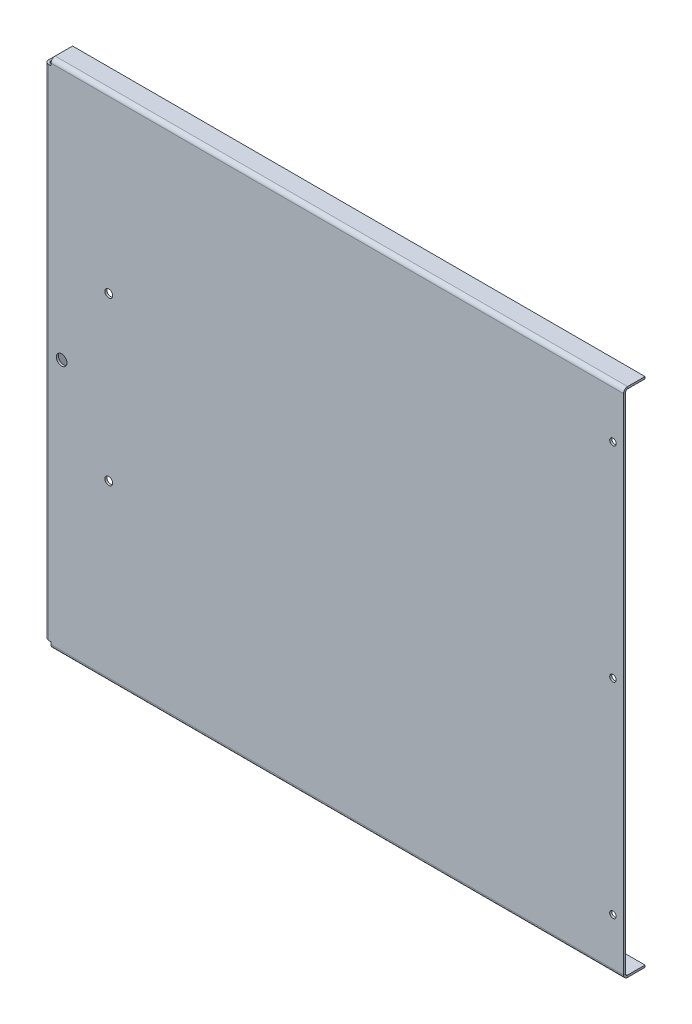
SolidWorks part; units mm, degrees
note: The reader was unsure of these and kept them because the rebuilt part matched: flange length of "Brida de arista1".
ref_plane "Alzado" through (0, 0, 0) normal (0, 0, 1) x (1, 0, 0)
ref_plane "Planta" through (0, 0, 0) normal (0, 1, 0) x (1, 0, 0)
ref_plane "Vista lateral" through (0, 0, 0) normal (1, 0, 0) x (0, 0, -1)
sketch "Croquis1" plane through (0, 0, 0) normal (0, 0, 1) x (1, 0, 0)
  line L1 (-215.519, -190.5) -> (215.519, -190.5)
  line L2 (-215.519, -190.5) -> (-215.519, 190.5)
  line L3 (-215.519, 190.5) -> (215.519, 190.5)
  line L4 (215.519, -190.5) -> (215.519, 190.5)
  line L5 (-215.519, -190.5) -> (215.519, 190.5) construction
  line L6 (-215.519, 190.5) -> (215.519, -190.5) construction
  point P0 (0, 0)
  dimension "D1" = 381
  dimension "D2" = 431.038
base flange "Brida base1" sketch "Croquis1" thickness 1.524 reverse thickness direction no parameters "D1"=1.524
sketch "Croquis6" plane through (0, 0, 0) normal (0, 0, 1) x (1, 0, 0)
  line L1 (-215.519, 190.5) -> (-210.693, 190.5)
  line L2 (-215.519, 190.5) -> (-215.519, 185.674)
  line L3 (-215.519, 185.674) -> (-210.693, 185.674)
  line L4 (-210.693, 190.5) -> (-210.693, 185.674)
  line L5 (-215.519, -190.5) -> (-210.693, -190.5)
  line L6 (-215.519, -190.5) -> (-215.519, -185.674)
  line L7 (-215.519, -185.674) -> (-210.693, -185.674)
  line L8 (-210.693, -190.5) -> (-210.693, -185.674)
  dimension "D1" = 4.826
  dimension "D2" = 4.826
extrude "Cortar-Extruir1" cut sketch "Croquis6" against normal up to next normal cut yes
edge flange "Brida de arista1" sketch "Croquis13" flange profiles "Croquis13", "Croquis14", "Croquis15" flange angle 90 flange length 16.002 flange position material inside bend radius 1.524 thickness 1.524 relief rectangular gap distance 1 parameters "D6"=10, "D8"=1
sketch "Croquis13" plane through (0, 190.5, -1.524) normal (0, 1, 0) x (1, 0, 0)
  line L0 (215.519, 0) -> (-210.693, 0) construction
  line L1 (215.519, 0) -> (-210.693, 0)
  line L2 (-210.693, 0) -> (-210.693, 14.478)
  line L3 (-210.693, 14.478) -> (215.519, 14.478)
  line L4 (215.519, 14.478) -> (215.519, 0)
sketch "Croquis14" plane through (0, -190.5, -1.524) normal (0, -1, 0) x (-1, 0, 0)
  line L0 (210.693, 0) -> (-215.519, 0) construction
  line L1 (210.693, 0) -> (-215.519, 0)
  line L2 (-215.519, 0) -> (-215.519, 14.478)
  line L3 (-215.519, 14.478) -> (210.693, 14.478)
  line L4 (210.693, 14.478) -> (210.693, 0)
sketch "Croquis15" plane through (-215.519, 0, -1.524) normal (-1, 0, 0) x (0, 1, 0)
  line L0 (185.674, 0) -> (-185.674, 0) construction
  line L1 (185.674, 0) -> (-185.674, 0)
  line L2 (-185.674, 0) -> (-185.674, 14.478)
  line L3 (-185.674, 14.478) -> (185.674, 14.478)
  line L4 (185.674, 14.478) -> (185.674, 0)
bend "Pliegue de arista1" bend radius 1.524 bend angle 90 parameters "D5"=1
bend "Pliegue de arista2" bend radius 1.524 bend angle 90 parameters "D5"=2
bend "Pliegue de arista3" bend radius 1.524 bend angle 90 parameters "D5"=3
sketch "Croquis16" plane through (0, 0, 0) normal (0, 0, 1) x (1, 0, 0)
  line L0 (215.519, -187.452) -> (215.519, 187.452) construction
  line L1 (215.519, 190.5) -> (-210.693, 190.5) construction
  line L2 (-210.693, -190.5) -> (215.519, -190.5) construction
  circle A0 centre (-202.819, 0) radius 3.9624
  circle A1 centre (-167.767, 60.452) radius 2.8956
  circle A2 centre (-167.767, -60.452) radius 2.8956
  circle A3 centre (207.645, 152.4) radius 2.413
  circle A4 centre (207.645, 0) radius 2.413
  circle A5 centre (207.645, -152.4) radius 2.413
  dimension "D1" = 60.452
  dimension "D2" = 60.452
  dimension "D8" = 4.826
  dimension "D9" = 5.7912
  dimension "D10" = 7.9248
  dimension "D3" = 383.286
  dimension "D4" = 418.338
  dimension "D5" = 38.1
  dimension "D6" = 38.1
  dimension "D7" = 7.874
extrude "Cortar-Extruir2" cut sketch "Croquis16" against normal up to next normal cut yes
sketch "Líneas de pliegue1" [suppressed] plane through (0, 0, 0) normal (0, 1, 0) x (1, 0, 0)
sketch "Cuadro delimitador1" [suppressed] plane through (0, 0, 0) normal (0, 1, 0) x (1, 0, 0)
sheet metal parameters "Chapa metálica1" thickness 1.524 parameters "D1"=1.524
flat pattern "Chapa desplegada1" [suppressed]
sketch "Líneas de pliegue2" plane through (0, 0, 0) normal (0, 1, 0) x (1, 0, 0)
sketch3d "Cuadro delimitador2" [suppressed]
  line L0 (215.519, -190.5, 0) -> (-215.519, -190.5, 0) construction
  line L1 (215.519, 190.5, 0) -> (-215.519, 190.5, 0) construction
  line L2 (215.519, -190.5, 0) -> (215.519, 190.5, 0) construction
  line L3 (-215.519, -190.5, 0) -> (-215.519, 190.5, 0) construction
sheet metal parameters "Chapa metálica2" thickness 1.524 parameters "D1"=1.524
flat pattern "Chapa desplegada1"
sketch "Líneas de pliegue2" plane through (0, 0, 0) normal (0, 1, 0) x (1, 0, 0)
sketch3d "Cuadro delimitador2" [suppressed]
  line L0 (-215.519, -190.5, 0) -> (215.519, -190.5, 0) construction
  line L1 (-215.519, 190.5, 0) -> (215.519, 190.5, 0) construction
  line L2 (-215.519, -190.5, 0) -> (-215.519, 190.5, 0) construction
  line L3 (215.519, -190.5, 0) -> (215.519, 190.5, 0) construction
sheet metal parameters "Chapa metálica3" thickness 1.524 parameters "D1"=1.524
flat pattern "Chapa desplegada1"
sketch "Líneas de pliegue2" plane through (0, 0, 0) normal (0, 0, 1) x (1, 0, 0)
  line L0 (-214.2425, 185.674) -> (-214.2425, -185.674) construction
  line L1 (-210.693, -189.2235) -> (215.519, -189.2235) construction
  line L2 (215.519, 189.2235) -> (-210.693, 189.2235) construction
  line L3 (-214.2425, 185.674) -> (-214.2425, -185.674) construction
  line L4 (-210.693, -189.2235) -> (215.519, -189.2235) construction
  line L5 (215.519, 189.2235) -> (-210.693, 189.2235) construction
sketch3d "Cuadro delimitador2" [suppressed]
  line L0 (-228.968, -203.949, 0) -> (215.519, -203.949, 0) construction
  line L1 (-228.968, 203.949, 0) -> (215.519, 203.949, 0) construction
  line L2 (-228.968, -203.949, 0) -> (-228.968, 203.949, 0) construction
  line L3 (215.519, -203.949, 0) -> (215.519, 203.949, 0) construction
bend of the flat pattern "Aplanar-<Pliegue de arista1>1"
bend of the flat pattern "Aplanar-<Pliegue de arista2>1"
bend of the flat pattern "Aplanar-<Pliegue de arista3>1"
sheet metal parameters "Chapa metálica4" thickness 1.524 parameters "D1"=1.524
flat pattern "Chapa desplegada1"
sketch "Líneas de pliegue2" plane through (0, 0, 0) normal (0, 0, 1) x (1, 0, 0)
  line L0 (-214.2425, 185.674) -> (-214.2425, -185.674) construction
  line L1 (-210.693, -189.2235) -> (215.519, -189.2235) construction
  line L2 (215.519, 189.2235) -> (-210.693, 189.2235) construction
  line L3 (-214.2425, 185.674) -> (-214.2425, -185.674) construction
  line L4 (-210.693, -189.2235) -> (215.519, -189.2235) construction
  line L5 (215.519, 189.2235) -> (-210.693, 189.2235) construction
sketch3d "Cuadro delimitador2" [suppressed]
  line L0 (-228.968, -203.949, 0) -> (215.519, -203.949, 0) construction
  line L1 (-228.968, 203.949, 0) -> (215.519, 203.949, 0) construction
  line L2 (-228.968, -203.949, 0) -> (-228.968, 203.949, 0) construction
  line L3 (215.519, -203.949, 0) -> (215.519, 203.949, 0) construction
bend of the flat pattern "Aplanar-<Pliegue de arista1>1"
bend of the flat pattern "Aplanar-<Pliegue de arista2>1"
bend of the flat pattern "Aplanar-<Pliegue de arista3>1"
equation "\"A\"= 15"
equation "\"D1@Croquis1\"=\"A\""
